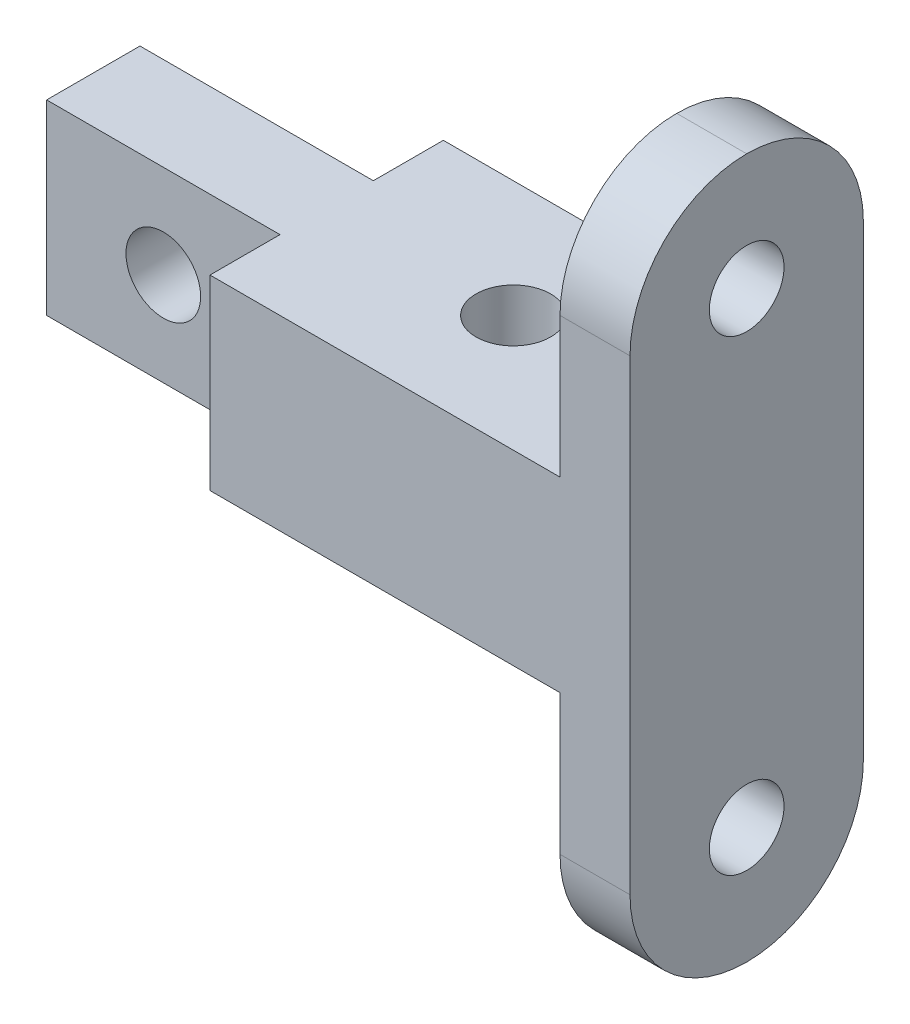
SolidWorks part; units mm, degrees
ref_plane "Plan de face" through (0, 0, 0) normal (0, 0, 1) x (1, 0, 0)
ref_plane "Plan de dessus" through (0, 0, 0) normal (0, 1, 0) x (1, 0, 0)
ref_plane "Plan de droite" through (0, 0, 0) normal (1, 0, 0) x (0, 0, -1)
sketch "Esquisse1" plane through (0, 0, 0) normal (0, 0, 1) x (1, 0, 0)
  line L0 (6, -4) -> (6, -15)
  line L2 (6, -4) -> (-19, -4)
  line L4 (6, 4) -> (-19, 4)
  line L7 (6, 15) -> (9, 15)
  line L8 (6, 15) -> (6, 4)
  line L9 (6, -15) -> (9, -15)
  line L10 (9, 15) -> (9, -15)
  line L11 (-19, -4) -> (-19, 4)
  point P0 (0, 0)
  point P10 (-11, 0)
  dimension "D1" = 3
  dimension "D2" = 25
  dimension "D3" = 30
  dimension "D4" = 15
  dimension "D5" = 8
  dimension "D6" = 11
  dimension "D7" = 19
extrude "Boss.-Extru.1" add sketch "Esquisse1" along normal blind 10
sketch "Esquisse2" plane through (6, 0, 0) normal (-1, 0, 0) x (0, 0, 1)
  line L0 (0, 15) -> (0, 4) construction
  line L1 (10, 15) -> (0, 15) construction
  circle A0 centre (5, 10) radius 1.6
  dimension "D1" = 3.2
  dimension "D2" = 5
  dimension "D3" = 5
extrude "Enlèv. mat.-Extru.1" cut sketch "Esquisse2" against normal blind 10
mirror "Symétrie3" about plane through (0, 0, 0) normal (0, 1, 0) of "Enlèv. mat.-Extru.1"
fillet "Congé1" radius 5 4 edges at (7.5, 15, 0) (7.5, 15, 10) (7.5, -15, 0) (7.5, -15, 10)
sketch "Esquisse3" plane through (0, 4, 0) normal (0, 1, 0) x (1, 0, 0)
  line L1 (-19, 0) -> (-9, 0)
  line L2 (-19, 0) -> (-19, -3)
  line L3 (-19, -3) -> (-9, -3)
  line L4 (-9, 0) -> (-9, -3)
  line L5 (-19, -10) -> (-9, -10)
  line L6 (-19, -10) -> (-19, -7)
  line L7 (-19, -7) -> (-9, -7)
  line L8 (-9, -10) -> (-9, -7)
  dimension "D1" = 3
  dimension "D2" = 3
  dimension "D3" = 10
  dimension "D4" = 10
extrude "Enlèv. mat.-Extru.2" cut sketch "Esquisse3" against normal blind 10
sketch "Esquisse4" plane through (0, 0, 3) normal (0, 0, -1) x (-1, 0, 0)
  line L0 (19, -4) -> (19, 4) construction
  line L1 (19, 4) -> (9, 4) construction
  circle A0 centre (14, 0) radius 1.6
  dimension "D1" = 3.2
  dimension "D2" = 5
  dimension "D3" = 4
extrude "Enlèv. mat.-Extru.3" cut sketch "Esquisse4" against normal blind 10
sketch "Esquisse5" plane through (0, -4, 0) normal (0, -1, 0) x (1, 0, 0)
  line L0 (6, 10) -> (6, 0) construction
  line L1 (-9, 0) -> (6, 0) construction
  circle A0 centre (-1, 5) radius 1.6
  dimension "D1" = 3.2
  dimension "D2" = 7
  dimension "D3" = 5
extrude "Enlèv. mat.-Extru.4" cut sketch "Esquisse5" against normal blind 10
